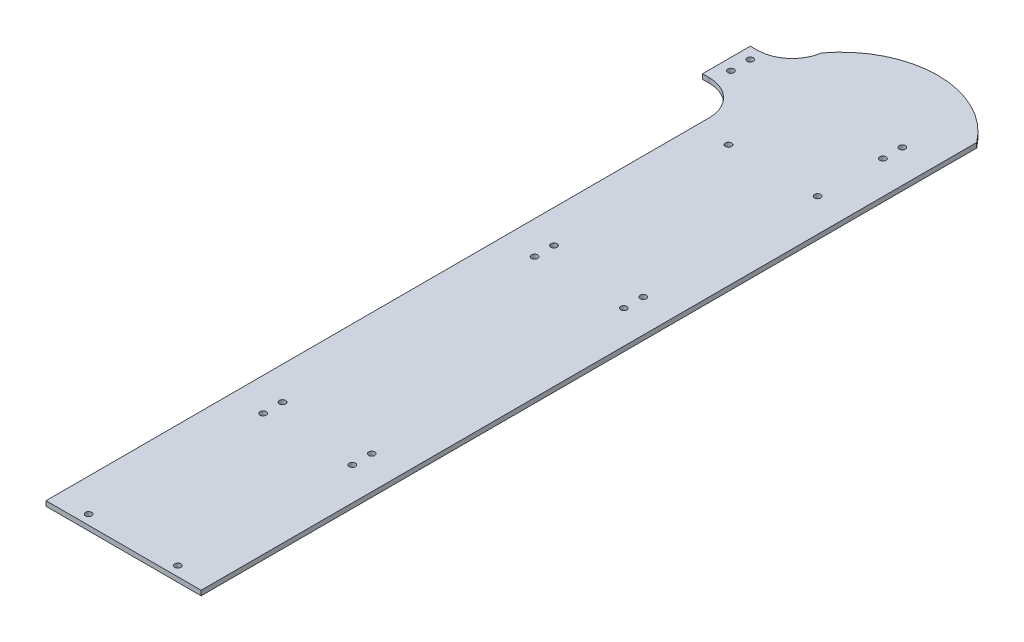
SolidWorks part; units mm, degrees
ref_plane "Front Plane" through (0, 0, 0) normal (0, 0, 1) x (1, 0, 0)
ref_plane "Top Plane" through (0, 0, 0) normal (0, 1, 0) x (1, 0, 0)
ref_plane "Right Plane" through (0, 0, 0) normal (1, 0, 0) x (0, 0, -1)
sketch "Sketch1" plane through (0, 0, 0) normal (0, 1, 0) x (1, 0, 0)
  line L2 (0, 0) -> (0, -508)
  line L3 (0, -508) -> (101.6, -508)
  line L4 (101.6, 0) -> (101.6, -508)
  arc A0 (0, 0) -> (101.6, 0) centre (50.8, -38.1) cw
  dimension "D3" = 63.5
  dimension "D1" = 508
  dimension "D2" = 101.6
extrude "Boss-Extrude1" add sketch "Sketch1" along normal blind 3.175
sketch "Sketch2" plane through (0, 0, 0) normal (0, -1, 0) x (1, 0, 0)
  line L0 (21.59, 82.55) -> (80.01, 82.55) construction
  line L1 (0, 508) -> (101.6, 508) construction
  circle A0 centre (21.59, 501.65) radius 2.032
  circle A1 centre (80.01, 501.65) radius 2.032
  circle A2 centre (21.59, 82.55) radius 2.032
  circle A3 centre (80.01, 82.55) radius 2.032
  arc A4 (0, 0) -> (101.6, 0) centre (50.8, 38.1) ccw construction
  circle A5 centre (21.59, 209.55) radius 2.032
  circle A6 centre (80.01, 209.55) radius 2.032
  circle A7 centre (21.59, 196.85) radius 2.032
  circle A8 centre (80.01, 196.85) radius 2.032
  circle A9 centre (21.59, 374.65) radius 2.032
  circle A10 centre (80.01, 374.65) radius 2.032
  circle A11 centre (21.59, 387.35) radius 2.032
  circle A12 centre (80.01, 387.35) radius 2.032
  point P11 (50.8, -25.4)
  point P12 (50.8, 82.55)
  dimension "D1" = 4.064
  dimension "D2" = 58.42
  dimension "D3" = 6.35
  dimension "D4" = 419.1
  dimension "D5" = 114.3
  dimension "D6" = 177.8
  dimension "D7" = 12.7
  dimension "D8" = 12.7
extrude "Cut-Extrude1" cut sketch "Sketch2" against normal through all
sketch "Sketch6" plane through (0, 3.175, 0) normal (0, 1, 0) x (1, 0, 0)
sketch "Sketch10" plane through (0, 0, 0) normal (0, -1, 0) x (-1, 0, 0)
  line L2 (0, 0) -> (76.2, 0)
  line L3 (0, 0) -> (0, -50.8)
  line L4 (0, -50.8) -> (76.2, -50.8)
  line L5 (76.2, 0) -> (76.2, -50.8)
  dimension "D1" = 50.8
  dimension "D2" = 76.2
extrude "Boss-Extrude6" add sketch "Sketch10" against normal up to surface (3.175 mm away) up to face at (80.01, 3.175, 207.518)
sketch "Sketch8" plane through (0, 0, 0) normal (0, -1, 0) x (-1, 0, 0)
  line L0 (-80.01, -80.518) -> (-80.01, -50.8583) construction
  line L1 (0, -508) -> (-101.6, -508) construction
  circle A0 centre (19.558, -39.7965) radius 2.032
  circle A1 centre (-80.01, -39.7965) radius 2.032
  circle A2 centre (19.558, -27.0965) radius 2.032
  circle A3 centre (-80.01, -27.0965) radius 2.032
  circle A4 centre (-80.01, -82.55) radius 2.032 construction
  point P13 (0, 0)
  dimension "D1" = 4.064
  dimension "D2" = 99.568
  dimension "D3" = 12.7
  dimension "D4" = 468.2035
sketch "Sketch11" plane through (0, 0, 0) normal (0, -1, 0) x (-1, 0, 0)
  line L1 (76.2, 0) -> (0, 0)
  line L2 (76.2, 0) -> (76.2, -19.4765)
  line L3 (76.2, -19.4765) -> (0, -19.4765)
  line L4 (0, 0) -> (0, -19.4765)
  line L5 (76.2, -50.8) -> (27.178, -50.8)
  line L6 (76.2, -50.8) -> (76.2, -19.4765)
  line L7 (76.2, -19.4765) -> (27.178, -19.4765)
  line L8 (27.178, -50.8) -> (27.178, -19.4765)
  line L10 (0, -50.8) -> (76.2, -50.8)
  line L11 (0, -50.8) -> (0, -47.4165)
  line L12 (0, -47.4165) -> (76.2, -47.4165)
  line L13 (76.2, -50.8) -> (76.2, -47.4165)
  line M25 (0, -50.8) -> (76.2, -50.8)
  line M26 (76.2, -50.8) -> (76.2, 0)
  line M27 (76.2, 0) -> (0, 0)
  dimension "D1" = 3.3835
  dimension "D2" = 7.62
  dimension "D3" = 7.62
extrude "Cut-Extrude3" cut sketch "Sketch11" against normal through all contours L8 L12 L6 L3 | L12 L8 M25 M26 | L4 L3 M27 M26 region at (-38.1, 0, 9.7382) region at (-51.689, 0, 33.4465) region at (-51.689, 0, 49.1082)
extrude "Cut-Extrude4" cut sketch "Sketch8" against normal through all
fillet "Fillet1" radius 22.86 2 edges at (0, 1.5875, 19.4765) (0, 1.5875, 50.8)
